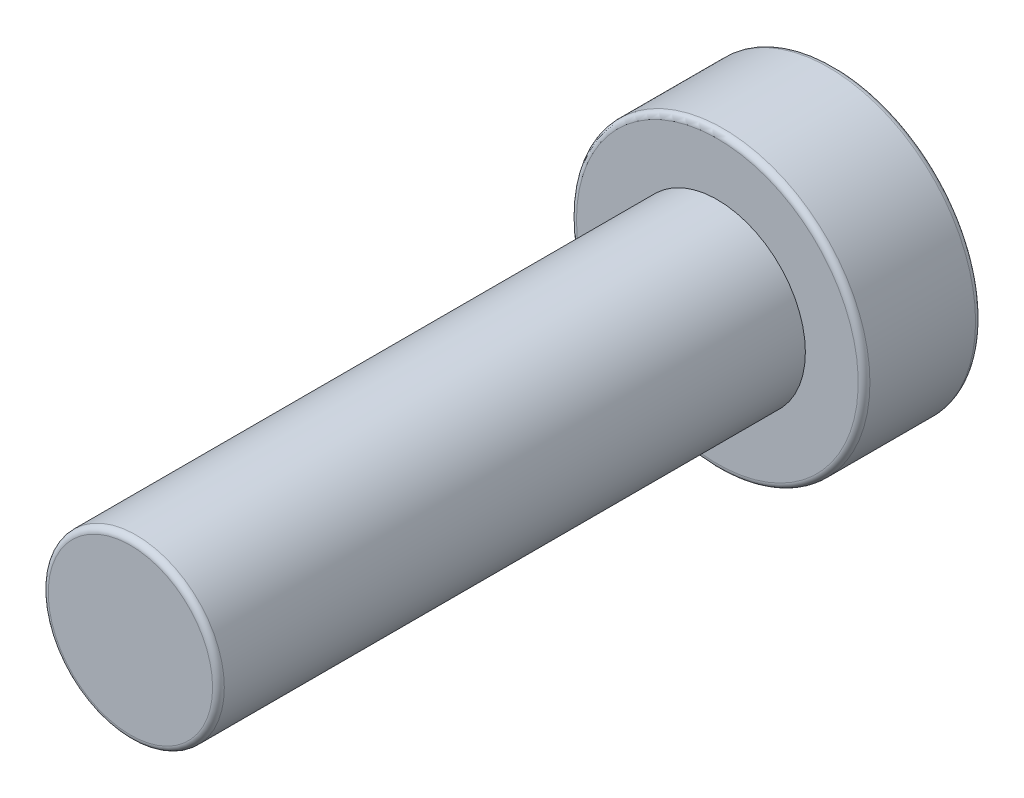
SolidWorks part; units mm, degrees
ref_plane "Alzado" through (0, 0, 0) normal (0, 0, 1) x (1, 0, 0)
ref_plane "Planta" through (0, 0, 0) normal (0, 1, 0) x (1, 0, 0)
ref_plane "Vista lateral" through (0, 0, 0) normal (1, 0, 0) x (0, 0, -1)
sketch "Croquis1" plane through (0, 0, 0) normal (0, 0, 1) x (1, 0, 0)
  circle A1 centre (0, 0) radius 1.5
  dimension "D1" = 3
extrude "Saliente-Extruir1" add sketch "Croquis1" along normal blind 10 contours A1
sketch "Croquis3" plane through (0, 0, 0) normal (0, 0, -1) x (-1, 0, 0)
  circle A0 centre (0, 0) radius 2.5
  dimension "D1" = 5
extrude "Saliente-Extruir3" add sketch "Croquis3" along normal blind 2
sketch "Croquis4" plane through (0, 0, -2) normal (0, 0, -1) x (-1, 0, 0)
  line L1 (1.5, 0) -> (0.75, 1.299)
  line L2 (0.75, 1.299) -> (-0.75, 1.299)
  line L3 (-0.75, 1.299) -> (-1.5, 0)
  line L4 (-1.5, 0) -> (-0.75, -1.299)
  line L5 (-0.75, -1.299) -> (0.75, -1.299)
  line L6 (0.75, -1.299) -> (1.5, 0)
  circle A0 centre (0, 0) radius 1.299 construction
  dimension "D1" = 3
extrude "Cortar-Extruir1" cut sketch "Croquis4" against normal blind 1.5
fillet "Redondeo4" radius 0.1 1 edges at (-2.5, 0, -2)
fillet "Redondeo5" radius 0.1 1 edges at (-2.5, 0, 0)
fillet "Redondeo6" radius 0.1 1 edges at (1.5, 0, 10)
